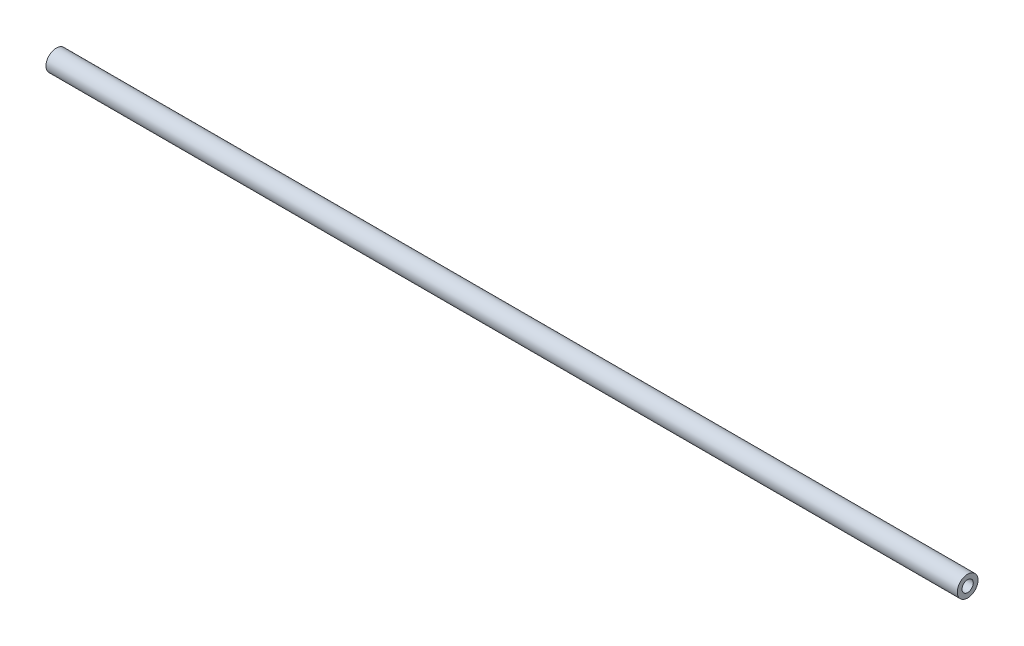
SolidWorks part; units mm, degrees
material "Plain Carbon Steel"
ref_plane "Front Plane" through (0, 0, 0) normal (0, 0, 1) x (1, 0, 0)
ref_plane "Top Plane" through (0, 0, 0) normal (0, 1, 0) x (1, 0, 0)
ref_plane "Right Plane" through (0, 0, 0) normal (1, 0, 0) x (0, 0, -1)
sketch "Sketch1" plane through (0, 0, 0) normal (1, 0, 0) x (0, 0, -1)
  circle A0 centre (0, 0) radius 3.175
  dimension "D1" = 6.35
extrude "Boss-Extrude1" add sketch "Sketch1" along normal mid plane 279.4
hole_wizard "Tap Drill for #8-32 Tap1" positions "Sketch2" profile "Sketch4" hole size "#8-32" standard "ANSI Inch"
sketch "Sketch2" plane through (139.7, 0, 0) normal (1, 0, 0) x (0, 0, -1)
  point P0 (0, 0)
sketch "Sketch4" plane through (139.7, 0, 0) normal (0, 1, 0) x (0, 0, -1)
  line L0 (0, 0) -> (0, 11.1978)
  line L1 (0, 11.1978) -> (1.7272, 10.16)
  line L2 (1.7272, 10.16) -> (1.7272, 0)
  line L5 (1.7272, 0) -> (0, 0)
  line L10 (0, 11.1978) -> (-1.7272, 10.16) construction
  line L11 (0, -6.35) -> (0, 107.95) construction
  dimension "Hole Dia." = 3.4544
  dimension "Hole Depth" = 10.16
  dimension "Drill Angle" = 118
mirror "Mirror1" about plane through (0, 0, 0) normal (1, 0, 0) of "Tap Drill for #8-32 Tap1"
